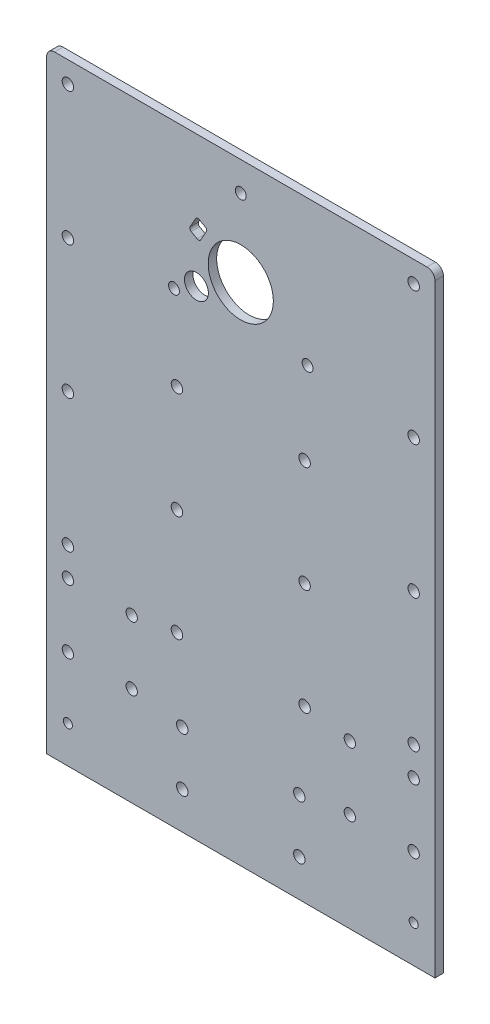
SolidWorks part; units mm, degrees
ref_plane "Front Plane" through (0, 0, 0) normal (0, 0, 1) x (1, 0, 0)
ref_plane "Top Plane" through (0, 0, 0) normal (0, 1, 0) x (1, 0, 0)
ref_plane "Right Plane" through (0, 0, 0) normal (1, 0, 0) x (0, 0, -1)
sketch "Sketch1" plane through (0, 0, 0) normal (0, 0, 1) x (1, 0, 0)
  line L0 (0, 115) -> (0, -115) construction
  line L1 (-73, -115) -> (73, -115)
  line L2 (-73, -115) -> (-73, 115)
  line L3 (-73, 115) -> (73, 115)
  line L4 (73, -115) -> (73, 115)
  line L5 (-73, -115) -> (73, 115) construction
  line L6 (-73, 115) -> (73, -115) construction
  line L7 (-53, -81.6804) -> (-53, -63.9214) construction
  line L10 (-65, -65.85) -> (-39.3402, -65.85) construction
  line L11 (-25.1147, 60.5) -> (0, 75) construction
  line L13 (-19.5167, 82.6867) -> (-15.4926, 80.458)
  line L18 (-15.4926, 80.458) -> (-12.4887, 85.8817)
  line L19 (-12.4887, 85.8817) -> (-16.5128, 88.1104)
  line L20 (-19.5167, 82.6867) -> (-16.5128, 88.1104)
  circle A0 centre (0, 75) radius 33.35 construction
  circle A1 centre (0, 75) radius 29 construction
  circle A2 centre (0, 104) radius 2.05
  circle A3 centre (25.1147, 60.5) radius 2.05
  circle A4 centre (-25.1147, 60.5) radius 2.05
  circle A10 centre (0, 75) radius 12.25
  circle A11 centre (-65, -77.85) radius 2.125
  circle A12 centre (-41, -77.85) radius 2.125
  circle A13 centre (-41, -53.85) radius 2.125
  circle A14 centre (-65, -53.85) radius 2.125
  circle A15 centre (41, -77.85) radius 2.125
  circle A16 centre (65, -77.85) radius 2.125
  circle A17 centre (65, -53.85) radius 2.125
  circle A18 centre (41, -53.85) radius 2.125
  circle A19 centre (-16.671, 65.375) radius 4.5
  circle A20 centre (-65, -101.025) radius 1.7
  circle A21 centre (65, -101.025) radius 1.7
  circle A22 centre (-65, 107) radius 2.15
  circle A23 centre (-65, 57) radius 2.15
  circle A24 centre (-65, 7) radius 2.15
  circle A25 centre (-65, -43) radius 2.15
  circle A26 centre (65, -43) radius 2.15
  circle A27 centre (65, 7) radius 2.15
  circle A28 centre (65, 57) radius 2.15
  circle A29 centre (65, 107) radius 2.15
  point P0 (0, 0)
  point P19 (0, 75)
  dimension "D3" = 66.7
  dimension "D4" = 40
  dimension "D5" = 58
  dimension "D6" = 4.1
  dimension "D8" = 4.25
  dimension "D9" = 8
  dimension "D10" = 37.15
  dimension "D12" = 24.5
  dimension "D14" = 9
  dimension "D19" = 3.4
  dimension "D24" = 4.3
  dimension "D1" = 146
  dimension "D2" = 230
  dimension "D11" = 12
  dimension "D13" = 12
  dimension "D15" = 19.25
  dimension "D16" = 4.6
  dimension "D17" = 6.2
  dimension "D18" = 90
  dimension "D20" = 8
  dimension "D21" = 13.975
  dimension "D22" = 26.8896
  dimension "D23" = 29.1183
  dimension "D25" = 8
  dimension "D26" = 8
  dimension "D27" = 4
  dimension "D7" = 3
extrude "Boss-Extrude1" add sketch "Sketch1" along normal blind 3.175
fillet "Fillet1" radius 1 4 edges at (-19.5167, 82.6867, 1.5875) (-15.4926, 80.458, 1.5875) (-12.4887, 85.8817, 1.5875) (-16.5128, 88.1104, 1.5875)
fillet "Fillet2" radius 3 2 edges at (73, 115, 1.5875) (-73, 115, 1.5875)
sketch "Sketch2" plane through (0, 0, 3.175) normal (0, 0, 1) x (1, 0, 0)
  line L0 (-73, -115) -> (73, -115) construction
  line L1 (-30, -115) -> (30, -115) construction
  line L2 (-30, -115) -> (-30, 35) construction
  line L3 (-30, 35) -> (30, 35) construction
  line L4 (30, -115) -> (30, 35) construction
  line L5 (0, 35) -> (0, -115) construction
  circle A0 centre (-22, -101.025) radius 2.15
  circle A1 centre (-22, -80.821) radius 2.15
  circle A2 centre (22, -101.025) radius 2.15
  circle A3 centre (22, -80.821) radius 2.15
  circle A4 centre (-24, 29) radius 2.15
  circle A5 centre (-24, -11) radius 2.15
  circle A6 centre (-24, -51) radius 2.15
  circle A7 centre (24, -51) radius 2.15
  circle A8 centre (24, -11) radius 2.15
  circle A9 centre (24, 29) radius 2.15
  dimension "D4" = 4.3
  dimension "D8" = 4.3
  dimension "D9" = 4.3
  dimension "D1" = 60
  dimension "D2" = 150
  dimension "D3" = 0
  dimension "D5" = 13.975
  dimension "D6" = 8
  dimension "D7" = 34.179
  dimension "D10" = 6
  dimension "D11" = 6
  dimension "D13" = 40
  dimension "D12" = 3
extrude "Cut-Extrude1" cut sketch "Sketch2" against normal through all
